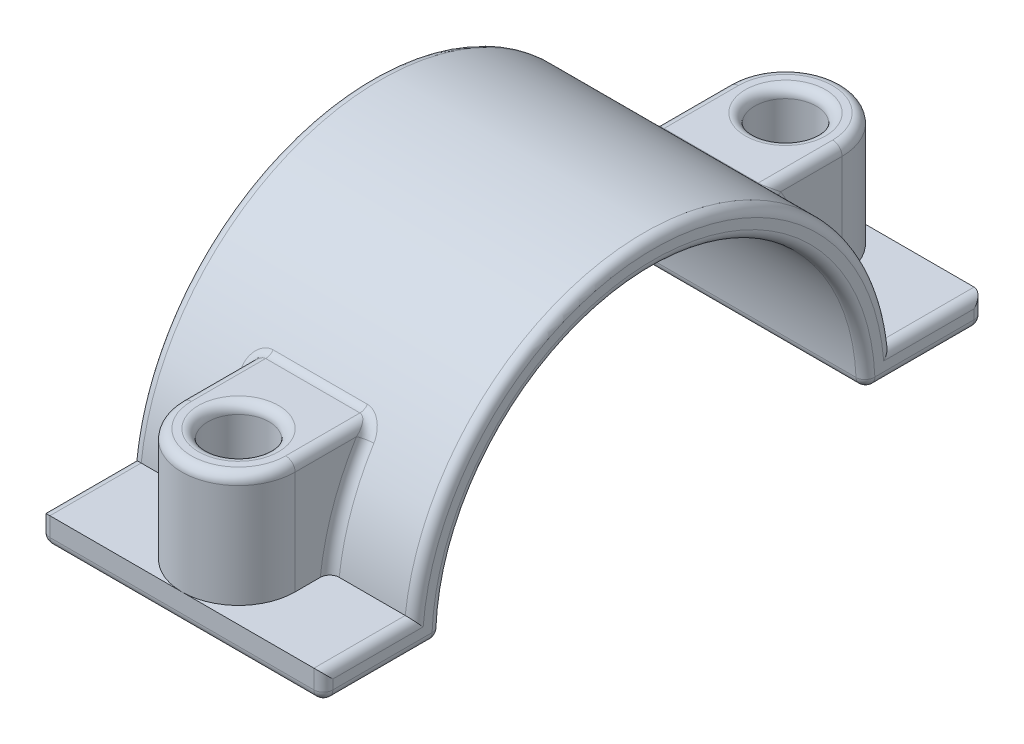
SolidWorks part; units mm, degrees
material "1023 Carbon Steel Sheet (SS)"
ref_plane "Front Plane" through (0, 0, 0) normal (0, 0, 1) x (1, 0, 0)
ref_plane "Top Plane" through (0, 0, 0) normal (0, 1, 0) x (1, 0, 0)
ref_plane "Right Plane" through (0, 0, 0) normal (1, 0, 0) x (0, 0, -1)
sketch "Sketch1" plane through (0, 0, 0) normal (1, 0, 0) x (0, 0, -1)
  line L0 (22.5, 0) -> (35, 0)
  line L1 (0, 22.5) -> (0, 0) construction
  line L2 (-22.5, 0) -> (-35, 0)
  line L3 (25.3229, 3) -> (35, 3)
  line L4 (-25.3229, 3) -> (-35, 3)
  line L5 (-35, 3) -> (-35, 0)
  line L6 (35, 3) -> (35, 0)
  arc A0 (22.5, 0) -> (-22.5, 0) centre (0, 0) ccw
  arc A1 (25.3229, 3) -> (-25.3229, 3) centre (0, 0) ccw
  dimension "D1" = 45
  dimension "D2" = 35
  dimension "D3" = 3
extrude "Boss-Extrude1" add sketch "Sketch1" along normal mid plane 30
ref_plane "Plane1" through (0, 15, 0) normal (0, 1, 0) x (1, 0, 0)
sketch "Sketch2" plane through (0, 15, 0) normal (0, 1, 0) x (1, 0, 0)
  line L0 (0, 0) -> (0, -35) construction
  line L1 (15, -35) -> (-15, -35) construction
  line L4 (6, -29) -> (6, -19)
  line L5 (6, -19) -> (-6, -19)
  line L6 (-6, -29) -> (-6, -19)
  arc A0 (-6, -29) -> (6, -29) centre (0, -29) ccw
  dimension "D1" = 12
  dimension "D2" = 10
extrude "Boss-Extrude2" add sketch "Sketch2" against normal up to body
sketch "Sketch3" plane through (0, 15, 0) normal (0, 1, 0) x (1, 0, 0)
  circle A0 centre (0, -29) radius 3.25
  dimension "D1" = 6.5
extrude "Cut-Extrude1" cut sketch "Sketch3" against normal through all
mirror "Mirror1" about plane through (0, 0, 0) normal (0, 0, 1) of "Cut-Extrude1", "Boss-Extrude2"
fillet "Fillet1" radius 1 36 edges at (6, 9.3019, -23.7429) (-6, 9.3019, -23.7429) (-6, 9.3019, 23.7429) (6, 9.3019, 23.7429) (-15, 3, 30.1615) (-15, 1.5, 35) (-15, 1.5, -35) (-15, 3, -30.1615) (-15, 25.5, 0) (15, 3, -30.1615) (15, 1.5, -35) (15, 1.5, 35) (15, 3, 30.1615) (15, 25.5, 0) (15, 22.5, 0) (-15, 22.5, 0) (0, 0, 35) (15, 0, 28.75) (0, 0, 22.5) (-15, 0, 28.75) (0, 0, 32.25) (0, 0, -22.5) (15, 0, -28.75) (0, 0, -35) (-15, 0, -28.75) (0, 0, -32.25) (0, 15, -35) (6, 15, -24.8108) (0, 15, -20.6216) (-6, 15, -24.8108) (0, 15, -32.25) (0, 15, 35) (-6, 15, 24.8108) (0, 15, 20.6216) (6, 15, 24.8108) (0, 15, 32.25)
